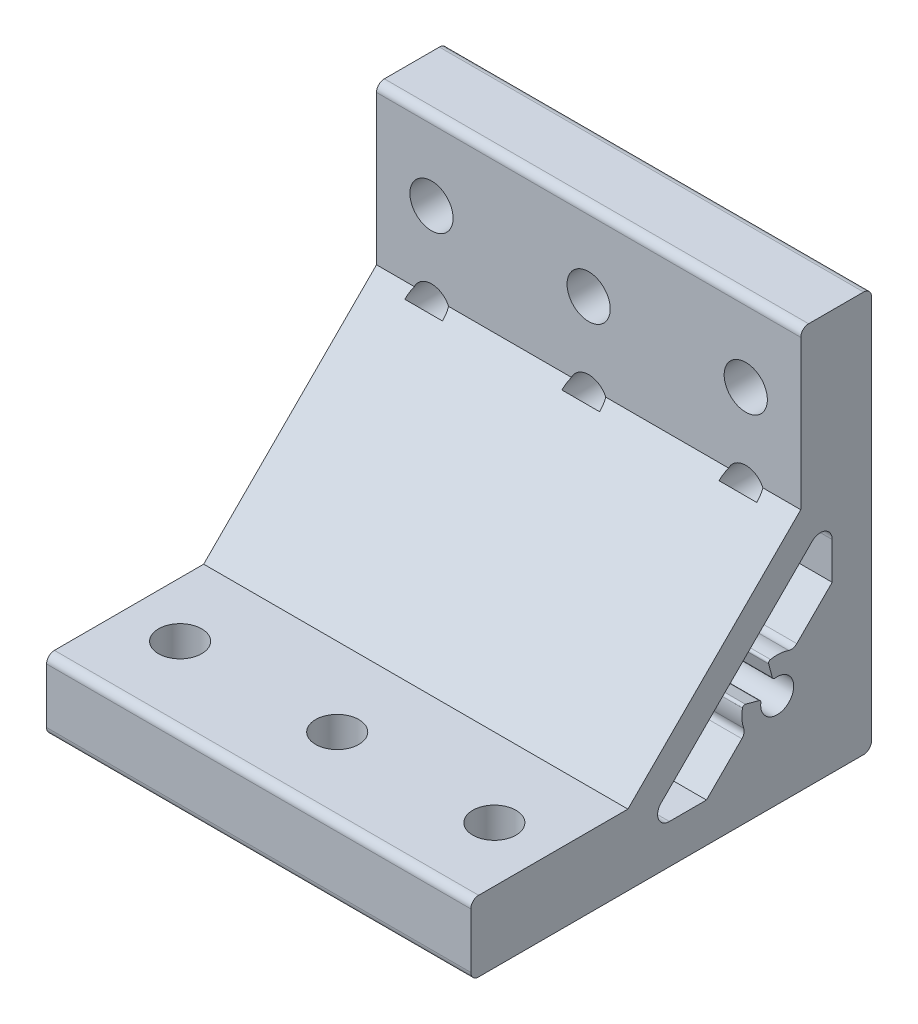
SolidWorks part; units mm, degrees
ref_plane "Front Plane" through (0, 0, 0) normal (0, 0, 1) x (1, 0, 0)
ref_plane "Top Plane" through (0, 0, 0) normal (0, 1, 0) x (1, 0, 0)
ref_plane "Right Plane" through (0, 0, 0) normal (1, 0, 0) x (0, 0, -1)
ref_plane "Plane1" through (0, 0, 0) normal (1, 0, 0) x (0, 0, -1)
sketch "Sketch1" plane through (0, 0, 0) normal (1, 0, 0) x (0, 0, -1)
  line L0 (-50, 0) -> (-1, 0)
  line L1 (0, 1) -> (0, 50)
  line L2 (-1, 51) -> (-8, 51)
  line L3 (-9, 50) -> (-9, 31)
  line L4 (-9, 31) -> (-31, 9)
  line L5 (-31, 9) -> (-50, 9)
  line L6 (-51, 8) -> (-51, 1)
  line L7 (-25.7218, 5) -> (-20.9993, 5)
  line L8 (-20.9993, 5) -> (-16.494, 9.5052)
  line L9 (-16.0465, 13.0843) -> (-14.3, 12.6163)
  line L10 (-12.6163, 14.3) -> (-13.0843, 16.0465)
  line L11 (-9.5052, 16.494) -> (-5, 20.9993)
  line L12 (-5, 20.9993) -> (-5, 25.7218)
  line L13 (-7.5607, 26.7825) -> (-26.7825, 7.5607)
  line L14 (-1, 0) -> (0, 0) construction
  line L15 (0, 0) -> (0, 1) construction
  line L16 (-1, 1) -> (-40.8569, 40.8569) construction
  arc A0 (-51, 1) -> (-50, 0) centre (-50, 1) ccw
  arc A1 (-1, 0) -> (0, 1) centre (-1, 1) ccw
  arc A2 (0, 50) -> (-1, 51) centre (-1, 50) ccw
  arc A3 (-8, 51) -> (-9, 50) centre (-8, 50) ccw
  arc A4 (-50, 9) -> (-51, 8) centre (-50, 8) ccw
  arc A5 (-26.7825, 7.5607) -> (-25.7218, 5) centre (-25.7218, 6.5) ccw
  arc A6 (-16.494, 9.5052) -> (-16.2556, 10.5372) centre (-17.2013, 10.2122) ccw
  arc A7 (-16.2556, 10.5372) -> (-16.4188, 12.8512) centre (-12, 12) cw
  arc A8 (-16.4188, 12.8512) -> (-16.0465, 13.0843) centre (-16.1242, 12.7945) cw
  arc A9 (-14.3, 12.6163) -> (-14.0805, 12.2857) centre (-14.3777, 12.3265) cw
  arc A10 (-14.0805, 12.2857) -> (-12.2857, 14.0805) centre (-12, 12) ccw
  arc A11 (-12.2857, 14.0805) -> (-12.6163, 14.3) centre (-12.3265, 14.3777) cw
  arc A12 (-13.0843, 16.0465) -> (-12.8512, 16.4188) centre (-12.7945, 16.1242) cw
  arc A13 (-12.8512, 16.4188) -> (-10.5377, 16.2558) centre (-12, 12) cw
  arc A14 (-10.5377, 16.2558) -> (-9.5052, 16.494) centre (-10.2122, 17.2013) ccw
  arc A15 (-5, 25.7218) -> (-7.5607, 26.7825) centre (-6.5, 25.7218) ccw
  dimension "D7" = 2.1
  dimension "D13" = 4.5
  dimension "D14" = 1
  dimension "D1" = 9
  dimension "D2" = 9
  dimension "D3" = 51
  dimension "D4" = 51
  dimension "D5" = 5
  dimension "D6" = 5
  dimension "D8" = 12
  dimension "D9" = 20
  dimension "D10" = 20
  dimension "D11" = 4
  dimension "D12" = 5.9
extrude "Boss-Extrude1" add sketch "Sketch1" against normal blind 27 and the other way blind 27
sketch "Sketch6" plane through (0, 0, 9) normal (0, 0, 1) x (1, 0, 0)
  line L0 (-20, 41) -> (20, 41) construction
  line L1 (0, 0) -> (0, 41) construction
  circle A0 centre (-20, 41) radius 2.75
  circle A1 centre (0, 41) radius 2.75
  circle A2 centre (20, 41) radius 2.75
  dimension "D3" = 5.5
  dimension "D1" = 20
  dimension "D2" = 41
extrude "Cut-Extrude5" cut sketch "Sketch6" against normal through all
sketch "Sketch7" plane through (0, 9, 0) normal (0, 1, 0) x (-1, 0, 0)
  line L0 (20, 41) -> (-20, 41) construction
  line L1 (0, 0) -> (0, 41) construction
  circle A0 centre (20, 41) radius 2.75
  circle A1 centre (0, 41) radius 2.75
  circle A2 centre (-20, 41) radius 2.75
  dimension "D2" = 5.5
  dimension "D1" = 41
  dimension "D3" = 20
extrude "Cut-Extrude6" cut sketch "Sketch7" against normal through all
sketch "Sketch9" plane through (0, 0, 0) normal (0, 0, -1) x (-1, 0, 0)
  circle A0 centre (20, 30) radius 2.4
  circle A1 centre (-20, 30) radius 2.4
  circle A2 centre (0, 30) radius 2.4
  circle A5 centre (20, 30) radius 2.75 construction
  circle A6 centre (-20, 30) radius 2.75 construction
  circle A7 centre (0, 30) radius 2.75 construction
  dimension "D1" = 4.8
extrude "Cut-Extrude7" cut sketch "Sketch9" against normal blind 10
